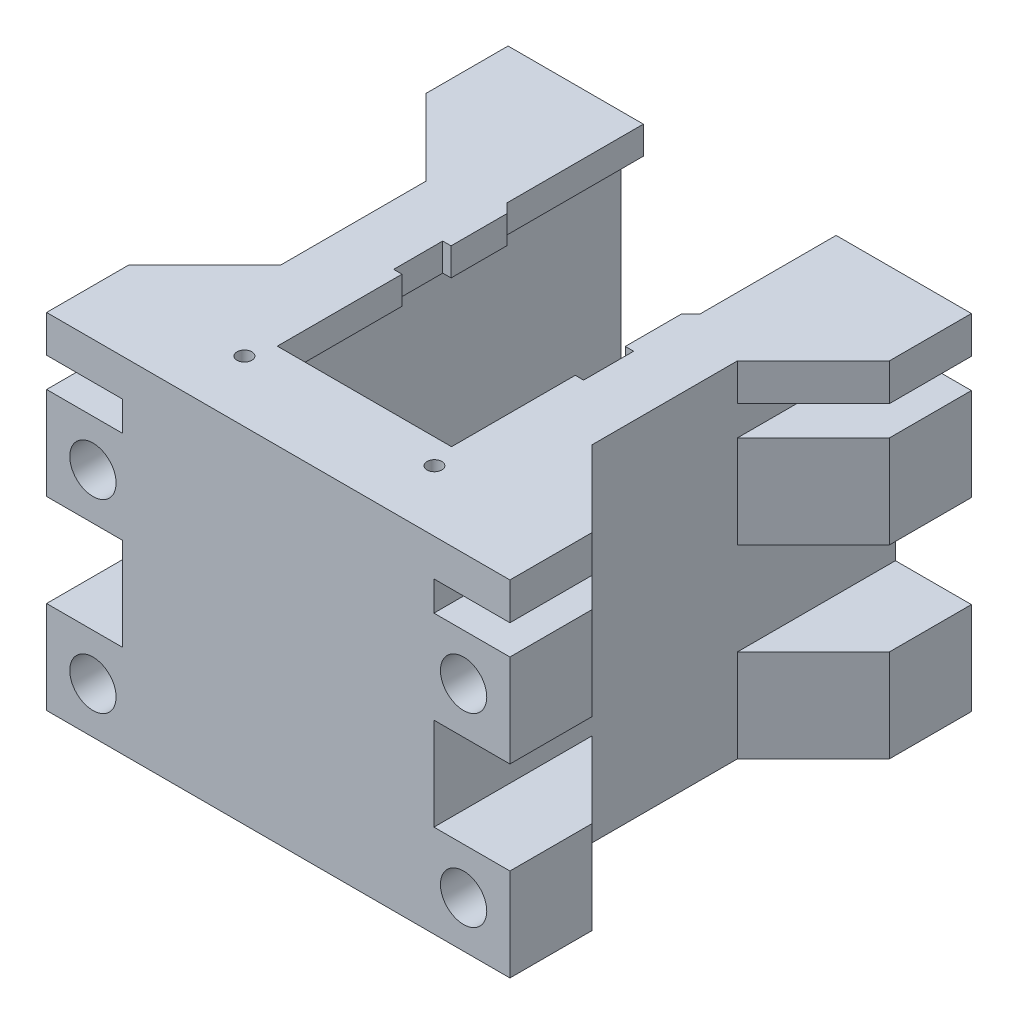
SolidWorks part; units mm, degrees
ref_plane "Front Plane" through (0, 0, 0) normal (0, 0, 1) x (1, 0, 0)
ref_plane "Top Plane" through (0, 0, 0) normal (0, 1, 0) x (1, 0, 0)
ref_plane "Right Plane" through (0, 0, 0) normal (1, 0, 0) x (0, 0, -1)
sketch "Sketch1" plane through (0, 0, 0) normal (0, 1, 0) x (1, 0, 0)
  line L0 (-9.2, -9.35) -> (9.2, -9.35) construction
  line L1 (-10.25, -12.25) -> (10.25, -12.25) construction
  line L2 (-10.25, -12.25) -> (-10.25, 12.25) construction
  line L3 (-10.25, 12.25) -> (10.25, 12.25) construction
  line L4 (10.25, -12.25) -> (10.25, 12.25) construction
  line L5 (-10.25, -12.25) -> (10.25, 12.25) construction
  line L6 (-10.25, 12.25) -> (10.25, -12.25) construction
  line L7 (0, -9.35) -> (0, 0) construction
  line L8 (-9.2, -9.35) -> (-9.2, 4) construction
  line L9 (-9.2, 4) -> (9.2, 4) construction
  line L10 (9.2, 4) -> (9.2, -9.35) construction
  line L11 (0, 8.05) -> (0, 0) construction
  line L12 (12.4, -14.65) -> (-12.4, -14.65) construction
  line L13 (12.4, -14.65) -> (12.4, 30.75) construction
  line L14 (12.4, 30.75) -> (-12.4, 30.75) construction
  line L15 (-12.4, -14.65) -> (-12.4, 30.75) construction
  line L16 (12.4, -14.65) -> (-12.4, 30.75) construction
  line L17 (12.4, 30.75) -> (-12.4, -14.65) construction
  line L18 (0, 20.55) -> (0, 8.05) construction
  line L19 (-9.4, -8.3) -> (-9.4, -18.85)
  line L20 (-7, -14.65) -> (7, -14.65) construction
  line L21 (-7, -14.65) -> (-7, 10.55) construction
  line L22 (-7, 10.55) -> (7, 10.55) construction
  line L23 (7, -14.65) -> (7, 10.55) construction
  line L24 (-7, -14.65) -> (7, 10.55) construction
  line L25 (-7, 10.55) -> (7, -14.65) construction
  line L26 (-16.8, -18.85) -> (16.8, -18.85)
  line L27 (-16.8, -18.85) -> (-16.8, 34.95)
  line L28 (-16.8, 34.95) -> (16.8, 34.95)
  line L29 (16.8, -18.85) -> (16.8, 34.95)
  line L30 (-16.8, -18.85) -> (16.8, 34.95) construction
  line L31 (-16.8, 34.95) -> (16.8, -18.85) construction
  line L32 (-12.8, -14.85) -> (12.8, -14.85)
  line L33 (-12.8, -14.85) -> (-12.8, 30.95)
  line L34 (-12.8, 30.95) -> (12.8, 30.95)
  line L35 (12.8, -14.85) -> (12.8, 30.95)
  line L36 (-12.8, -14.85) -> (12.8, 30.95) construction
  line L37 (-12.8, 30.95) -> (12.8, -14.85) construction
  line L38 (-7.2, -14.85) -> (7.2, -14.85) construction
  line L39 (-7.2, -14.85) -> (-7.2, 10.75)
  line L40 (-7.2, 10.75) -> (7.2, 10.75)
  line L41 (7.2, -14.85) -> (7.2, 10.75)
  line L42 (-7.2, -14.85) -> (7.2, 10.75) construction
  line L43 (-7.2, 10.75) -> (7.2, -14.85) construction
  line L44 (-9.4, -8.3) -> (9.4, -8.3) construction
  line L45 (-9.4, -8.3) -> (-9.4, 4.2)
  line L46 (-9.4, 4.2) -> (9.4, 4.2)
  line L47 (9.4, -8.3) -> (9.4, 4.2)
  line L48 (-9.4, -8.3) -> (9.4, 4.2) construction
  line L49 (-9.4, 4.2) -> (9.4, -8.3) construction
  line L50 (-7.2, -14.85) -> (-7.2, -18.85)
  line L51 (7.2, -14.85) -> (7.2, -18.85)
  line L52 (9.4, -8.3) -> (9.4, -18.85)
  line L53 (-12.8, -14.85) -> (-12.8, -18.85)
  line L54 (12.8, -14.85) -> (12.8, -18.85)
  line L55 (-12.8, -14.85) -> (-16.8, -14.85)
  line L56 (12.8, -14.85) -> (16.8, -14.85)
  line L57 (-10.3, 3.9) -> (-9.4, 3.9)
  line L58 (10.1, 9) -> (-10.1, 9) construction
  line L59 (10.1, 9) -> (10.1, 4) construction
  line L60 (10.1, 4) -> (-10.1, 4) construction
  line L61 (-10.1, 9) -> (-10.1, 4) construction
  line L62 (10.1, 9) -> (-10.1, 4) construction
  line L63 (10.1, 4) -> (-10.1, 9) construction
  line L64 (-10.3, 3.9) -> (-10.3, 9.2)
  line L65 (-10.3, 9.2) -> (10.3, 9.2)
  line L66 (10.3, 9.2) -> (10.3, 3.8)
  line L67 (10.3, 3.8) -> (9.4, 3.8)
  line L68 (-10.4, 30.95) -> (-10.4, 16.2422)
  line L69 (-10.4, 16.2422) -> (-4.9078, 10.75)
  line L70 (10.4, 16.2422) -> (4.9078, 10.75)
  line L71 (10.4, 30.95) -> (10.4, 16.2422)
  line L72 (-4.9078, 10.75) -> (-4.9078, 9.2)
  line L73 (4.9078, 10.75) -> (4.9078, 9.2)
  line L74 (-12.8, 30.95) -> (-12.8, 34.95)
  line L75 (12.8, 30.95) -> (12.8, 34.95)
  line L76 (-12.8, 30.95) -> (-16.8, 30.95)
  line L77 (12.8, 30.95) -> (16.8, 30.95)
  line L78 (-9.4, -9.55) -> (9.4, -9.55)
  line L79 (-9.4, 9.2) -> (-9.4, 15.2422)
  line L80 (9.4, 9.2) -> (9.4, 15.2422)
  line L81 (7.2, 10.75) -> (7.2, 13.0422)
  line L82 (-7.2, 10.75) -> (-7.2, 13.0422)
  circle A0 centre (-10.25, 12.25) radius 0.8
  circle A1 centre (10.25, 12.25) radius 0.8
  circle A2 centre (-10.25, -12.25) radius 0.8
  circle A3 centre (10.25, -12.25) radius 0.8
  circle A4 centre (0, 20.55) radius 10 construction
  circle A5 centre (0, 20.55) radius 10.4 construction
  circle A6 centre (-10.25, -8.45) radius 0.8
  circle A7 centre (10.25, -8.45) radius 0.8
  point P8 (0, 0)
  point P15 (0, -9.35)
  point P18 (0, 8.05)
  point P25 (0, -2.05)
  point P38 (0, -2.05)
  point P43 (0, -2.05)
  point P48 (0, 6.5)
  dimension "D1" = 1.6
  dimension "D9" = 2.4
  dimension "D11" = 20
  dimension "D27" = 0.2
  dimension "D30" = 6.2
  dimension "D2" = 24.5
  dimension "D3" = 20.5
  dimension "D4" = 18.4
  dimension "D5" = 2.9
  dimension "D6" = 13.35
  dimension "D7" = 24.8
  dimension "D8" = 45.4
  dimension "D10" = 10.2
  dimension "D12" = 14
  dimension "D13" = 4
  dimension "D14" = 4
  dimension "D15" = 0.4
  dimension "D16" = 0.4
  dimension "D17" = 0.2
  dimension "D18" = 0.2
  dimension "D19" = 0.2
  dimension "D20" = 0.2
  dimension "D21" = 5
  dimension "D22" = 20.2
  dimension "D23" = 0.2
  dimension "D24" = 0.2
  dimension "D25" = 0.2
  dimension "D26" = 45
  dimension "D28" = 0.2
  dimension "D29" = 0.2
extrude "Boss-Extrude2" add sketch "Sketch1" along normal blind 2.4 contours L33 L76 L27 L55 | L77 L35 L56 L29 | L56 L54 L26 L29 | L54 L32 L52 L26 | L52 L32 L41 L51 L26 | L51 L41 L32 L39 L50 L26 | L50 L39 L32 L19 L26 | L32 L53 L26 L19 | L53 L55 L27 L26 | L34 L71 L70 L40 L41 L65 L66 L47 L52 L32 L35 A3 A1 | L69 L68 L34 L33 L32 L19 L45 L64 L65 L39 L40 A2 A0 | L78 L19 L32 L39 | L78 L41 L32 L52 | L39 L82 L69 L79 L65 | L65 L64 L57 L45 L46 L39 | L19 L78 L39 L46 L45 | L41 L78 L52 L47 L46 | L67 L66 L65 L41 L46 L47 | L81 L41 L65 L80 L70 region at (-8.3, 0, 2.675) region at (-11.3268, 0, -6.8174) region at (-8.3, 0, 12.2) region at (-8.7688, 0, -6.6546) region at (-8.3, 0, 16.85) region at (-11.1, 0, 16.85) region at (-14.8, 0, -8.05) region at (-14.8, 0, 16.85) region at (0, 0, 16.85) region at (8.3, 0, 12.2) region at (8.3, 0, 2.675) region at (8.3, 0, 16.85) region at (-8.3816, 0, -11.7119) region at (8.775, 0, -6.6387) region at (11.3279, 0, -6.8195) region at (11.1, 0, 16.85) region at (8.3816, 0, -11.7119) region at (14.8, 0, 16.85) region at (14.8, 0, -8.05)
extrude "Boss-Extrude4" add sketch "Sketch1<6>" along normal offset from surface (34.2 mm away) 31.8 contours L33 L74 L28 L27 L55 | L77 L35 L56 L29 | L56 L54 L26 L29 | L54 L32 L52 L26 | L51 L41 L32 L39 L50 L26 | L32 L53 L26 L19 | L53 L55 L27 L26 | L50 L39 L32 L19 L26 | L52 L32 L41 L51 L26 region at (-8.3, 0, 16.85) region at (-11.1, 0, 16.85) region at (-14.8, 0, -8.05) region at (-14.8, 0, 16.85) region at (0, 0, 16.85) region at (8.3, 0, 16.85) region at (11.1, 0, 16.85) region at (14.8, 0, 16.85) region at (14.8, 0, -8.05) up to face at (0, 2.4, -9.5807) offset beyond the face yes
sketch "Sketch1<6>" plane through (0, 0, 0) normal (0, 1, 0) x (1, 0, 0) same geometry as "Sketch1"
extrude "Boss-Extrude7" add sketch "Sketch1<9>" along normal offset from surface (37.2 mm away) 3 contours L65 L79 L69 L68 L34 L33 L32 L19 L45 L57 L64 A2 A0 | L80 L65 L66 L67 L47 L52 L32 L35 L34 L71 L70 A3 A1 | L33 L76 L27 L55 | L53 L55 L27 L26 | L32 L53 L26 L19 | L50 L32 L19 L26 | L51 L32 L50 L26 | L52 L32 L51 L26 | L54 L32 L52 L26 | L56 L54 L26 L29 | L77 L35 L56 L29 | L78 L41 L32 L52 | L78 L19 L32 L39 | L78 L39 L32 L41 | A6 | A7 region at (-11.3268, 0, -6.8174) region at (-8.3, 0, 12.2) region at (-8.3, 0, 16.85) region at (-11.1, 0, 16.85) region at (0, 0, 12.2) region at (-14.8, 0, -8.05) region at (-14.8, 0, 16.85) region at (0, 0, 16.85) region at (8.3, 0, 12.2) region at (8.3, 0, 16.85) region at (11.3279, 0, -6.8195) region at (11.1, 0, 16.85) region at (14.8, 0, 16.85) region at (14.8, 0, -8.05) region at (-10.25, 0, 8.45) region at (10.25, 0, 8.45) up to face at (0, 34.2, -7.05) offset beyond the face yes
sketch "Sketch1<9>" plane through (0, 0, 0) normal (0, 1, 0) x (1, 0, 0) same geometry as "Sketch1"
extrude "Cut-Extrude6" cut sketch "Sketch1<10>" along normal offset from surface (34.2 mm away) 3 contours L67 L66 L65 L41 L46 L47 | L65 L64 L57 L45 L46 L39 | L19 L78 L39 L46 L45 | L41 L78 L52 L47 L46 | L39 L82 L69 L79 L65 | L81 L41 L65 L80 L70 | L65 L79 L69 L68 L34 L33 L32 L19 L45 L57 L64 A2 A0 | L80 L65 L66 L67 L47 L52 L32 L35 L34 L71 L70 A3 A1 | L39 L78 L41 L46 | L78 L39 L32 L41 | L78 L19 L32 L39 | L78 L41 L32 L52 | A2 | A3 | A6 | A7 region at (-8.3, 0, 2.675) region at (-11.3268, 0, -6.8174) region at (-8.3, 0, 12.2) region at (-8.7688, 0, -6.6546) region at (0, 0, 12.2) region at (0, 0, 2.675) region at (8.3, 0, 12.2) region at (8.3, 0, 2.675) region at (-8.3816, 0, -11.7119) region at (8.775, 0, -6.6387) region at (11.3279, 0, -6.8195) region at (8.3816, 0, -11.7119) region at (-10.25, 0, 12.25) region at (10.25, 0, 12.25) region at (-10.25, 0, 8.45) region at (10.25, 0, 8.45) up to face at (-10.25, 37.2, 13.05)
sketch "Sketch1<10>" plane through (0, 0, 0) normal (0, 1, 0) x (1, 0, 0) same geometry as "Sketch1"
extrude "Boss-Extrude8" add sketch "Sketch1<11>" along normal offset from surface (2 mm away) 2 contours L80 L65 L66 L67 L47 L52 L32 L35 L34 L71 L70 A3 A1 | L78 L41 L32 L52 | L65 L79 L69 L68 L34 L33 L32 L19 L45 L57 L64 A2 A0 | L78 L19 L32 L39 | L67 L66 L65 L41 L46 L47 | L41 L78 L52 L47 L46 | L65 L64 L57 L45 L46 L39 | L19 L78 L39 L46 L45 | L39 L82 L69 L79 L65 | L81 L41 L65 L80 L70 | A3 | A2 region at (-8.3, 0, 2.675) region at (-11.3268, 0, -6.8174) region at (-8.3, 0, 12.2) region at (-8.7688, 0, -6.6546) region at (8.3, 0, 12.2) region at (8.3, 0, 2.675) region at (-8.3816, 0, -11.7119) region at (8.775, 0, -6.6387) region at (11.3279, 0, -6.8195) region at (8.3816, 0, -11.7119) region at (-10.25, 0, 12.25) region at (10.25, 0, 12.25) up to face at (0, 0, -7.05)
sketch "Sketch1<11>" plane through (0, 0, 0) normal (0, 1, 0) x (1, 0, 0) same geometry as "Sketch1"
sketch "Sketch9" plane through (0, 0, 18.85) normal (0, 0, 1) x (1, 0, 0)
  line L0 (-16.8, 37.2) -> (-25, 37.2)
  line L1 (-25, 37.2) -> (-25, 0)
  line L2 (-25, 0) -> (-16.8, 0)
  line L3 (0, 0) -> (0, 37.2) construction
  line L4 (-16.8, 0) -> (16.8, 0) construction
  line L5 (-16.8, 37.2) -> (16.8, 37.2) construction
  line L6 (-20, 25) -> (-20, 5)
  line L7 (-25, 30) -> (-16.8, 30)
  line L8 (-16.8, 37.2) -> (-16.8, 0) construction
  line L9 (-25, 10) -> (-16.8, 10)
  line L10 (-25, 20) -> (-16.8, 20)
  line L11 (-25, 33.2) -> (-16.8, 33.2)
  line L12 (-16.8, 37.2) -> (-16.8, 0)
  line L13 (16.8, 37.2) -> (16.8, 0)
  line L14 (25, 0) -> (16.8, 0)
  line L15 (25, 33.2) -> (16.8, 33.2)
  line L16 (25, 20) -> (16.8, 20)
  line L17 (25, 10) -> (16.8, 10)
  line L18 (25, 30) -> (16.8, 30)
  line L19 (25, 37.2) -> (25, 0)
  line L20 (16.8, 37.2) -> (25, 37.2)
  circle A0 centre (-20, 25) radius 2.5
  circle A1 centre (-20, 5) radius 2.5
  circle A2 centre (20, 5) radius 2.5
  circle A3 centre (20, 25) radius 2.5
  line M12 (16.8, 0) -> (16.8, 37.2)
  line M14 (-16.8, 37.2) -> (-16.8, 0)
  dimension "D3" = 5
  dimension "D4" = 5
  dimension "D5" = 5
  dimension "D7" = 5
  dimension "D8" = 5
  dimension "D1" = 20
  dimension "D2" = 20
  dimension "D6" = 5
  dimension "D9" = 4
extrude "Boss-Extrude9" add sketch "Sketch9" against normal up to surface (49.8 mm away) contours A1 L9 L1 L2 M14 | A0 L10 L7 L1 M14 | L1 L11 L0 M14 | L19 L17 L14 A2 M12 | L19 L18 L13 L16 A3 | L20 L13 L15 L19 region at (-20.9, 35.2, 18.85) region at (-16.9293, 25, 18.85) region at (-16.9293, 5, 18.85) region at (20.9, 35.2, 18.85) region at (20.9, 29.8707, 18.85) region at (20.9, 9.8707, 18.85) up to face at (12.6, 18.35, -30.95)
extrude "Boss-Extrude10" add sketch "Sketch9<3>" against normal offset from surface (44.4 mm away) 5.4 contours A1 | A0 | A3 | A2 region at (-21.7178, 26.7178, 18.85) region at (-18.2822, 6.7178, 18.85) region at (20, 5, 18.85) region at (20, 25, 18.85) up to face at (-17.775, 20.825, -30.95)
sketch "Sketch9<3>" plane through (0, 0, 18.85) normal (0, 0, 1) x (1, 0, 0) same geometry as "Sketch9"
extrude "Cut-Extrude7" cut sketch "Sketch9<4>" against normal offset from surface (5.4 mm away) 5.4 contours A2 | A3 | A0 | A1 region at (-21.7178, 26.7178, 18.85) region at (-18.2822, 6.7178, 18.85) region at (20, 5, 18.85) region at (20, 25, 18.85) up to face at (0, 22.36, 18.85)
sketch "Sketch9<4>" plane through (0, 0, 18.85) normal (0, 0, 1) x (1, 0, 0) same geometry as "Sketch9"
sketch "Sketch12" plane through (0, 37.2, 0) normal (0, 1, 0) x (1, 0, 0)
  line L0 (0, 0) -> (0, -18.85) construction
  line L7 (-25, -18.85) -> (25, -18.85) construction
  line L8 (-25, 6.05) -> (0, 6.05) construction
  line L10 (-25, 30.95) -> (-25, -18.85) construction
  line L11 (-25, 22.0969) -> (-16.8, 22.0969)
  line L12 (-16.8, 22.0969) -> (-16.8, 24.0969)
  line L13 (-16.8, 24.0969) -> (-25, 24.0969)
  line L14 (-25, 24.0969) -> (-25, 22.0969)
  line L15 (-25, 22.0969) -> (-16.8, 13.8969)
  line L16 (-16.8, 13.8969) -> (-16.8, 22.0969)
  line L17 (-16.8, 13.8969) -> (-16.8, -1.7969)
  line L18 (-16.8, -1.7969) -> (-16.8, -9.9969)
  line L21 (-25, -9.9969) -> (-16.8, -1.7969)
  line L24 (-25, -13.45) -> (-25, -9.9969)
  line L25 (-25, -9.9969) -> (-16.8, -9.9969)
  line L26 (-16.8, -9.9969) -> (-16.8, -13.45)
  line L27 (-16.8, -13.45) -> (-25, -13.45)
  line L29 (16.8, -9.9969) -> (16.8, -13.45)
  line L30 (16.8, -13.45) -> (25, -13.45)
  line L31 (25, -9.9969) -> (16.8, -9.9969)
  line L32 (25, -9.9969) -> (16.8, -1.7969)
  line L33 (16.8, -1.7969) -> (16.8, -9.9969)
  line L34 (16.8, 13.8969) -> (16.8, -1.7969)
  line L35 (16.8, 13.8969) -> (16.8, 22.0969)
  line L36 (25, 22.0969) -> (16.8, 13.8969)
  line L37 (25, 25.55) -> (25, 22.0969)
  line L38 (25, 22.0969) -> (16.8, 22.0969)
  line L39 (16.8, 22.0969) -> (16.8, 25.55)
  line L40 (16.8, 25.55) -> (25, 25.55)
  line L41 (-25, 22.0969) -> (-25, -9.9969)
  line L42 (25, 22.0969) -> (25, -9.9969)
  point P16 (-16.8, 6.05)
  line M19 (-25, 30.95) -> (-25, -18.85)
  line M21 (25, -18.85) -> (25, 30.95)
  dimension "D1" = 2
  dimension "D2" = 45
extrude "Cut-Extrude8" cut sketch "Sketch12" against normal up to surface (37.2 mm away) contours L21 L17 L15 M19 | L36 L34 L32 M21 region at (-21.369, 37.2, -6.05) region at (21.369, 37.2, -6.05) up to face at (0, 0, -9.5807)
sketch "Sketch14" plane through (0, 37.2, 0) normal (0, 1, 0) x (1, 0, 0)
  line L0 (-10.3, 9.2) -> (-10.3, 16.1422)
  line L13 (-10.25, 14.05) -> (-11.8088, 13.15) construction
  line L14 (-11.8088, 13.15) -> (-11.8088, 11.35) construction
  line L15 (-11.8088, 11.35) -> (-10.25, 10.45) construction
  line L16 (-10.25, 10.45) -> (-8.6912, 11.35) construction
  line L17 (-8.6912, 11.35) -> (-8.6912, 13.15) construction
  line L18 (-8.6912, 13.15) -> (-10.25, 14.05) construction
  line L19 (10.25, 14.05) -> (8.6912, 13.15) construction
  line L20 (8.6912, 13.15) -> (8.6912, 11.35) construction
  line L21 (8.6912, 11.35) -> (10.25, 10.45) construction
  line L22 (10.25, 10.45) -> (11.8088, 11.35) construction
  line L23 (11.8088, 11.35) -> (11.8088, 13.15) construction
  line L24 (11.8088, 13.15) -> (10.25, 14.05) construction
  line L25 (-10.4, 16.2422) -> (-9.4, 15.2422) construction
  line L26 (-10.3, 9.2) -> (-9.4, 9.2)
  line L27 (-9.4, 9.2) -> (-9.4, 15.2422) construction
  line L28 (-9.4, 9.2) -> (-9.4, 15.2422)
  line L29 (-9.4, 15.2422) -> (-10.3, 16.1422)
  line L30 (9.4, 9.2) -> (10.3, 9.2)
  line L31 (10.3, 9.2) -> (10.3, 16.1422)
  line L32 (10.4, 16.2422) -> (9.4, 15.2422) construction
  line L33 (10.3, 16.1422) -> (9.4, 15.2422)
  line L34 (9.4, 15.2422) -> (9.4, 9.2)
  circle A5 centre (-10.25, 12.25) radius 1.5588 construction
  circle A6 centre (10.25, 12.25) radius 1.5588 construction
  circle A9 centre (-10.25, 12.25) radius 1.8 construction
  circle A10 centre (-10.25, 12.25) radius 0.8 construction
  circle A11 centre (-10.25, 12.25) radius 0.8
  circle A12 centre (10.25, 12.25) radius 0.8
  circle M2 centre (10.25, 12.25) radius 0.8
  circle M4 centre (-10.25, 12.25) radius 0.8
  dimension "D1" = 1
extrude "Boss-Extrude12" add sketch "Sketch14" against normal up to surface (3 mm away) contours L0 M4 | L0 M4 | L31 M2 | L31 M2 region at (-10.6167, 37.2, -12.25) region at (-9.9373, 37.2, -12.25) region at (9.9373, 37.2, -12.25) region at (10.6167, 37.2, -12.25) up to face at (10.25, 34.2, 13.05)
